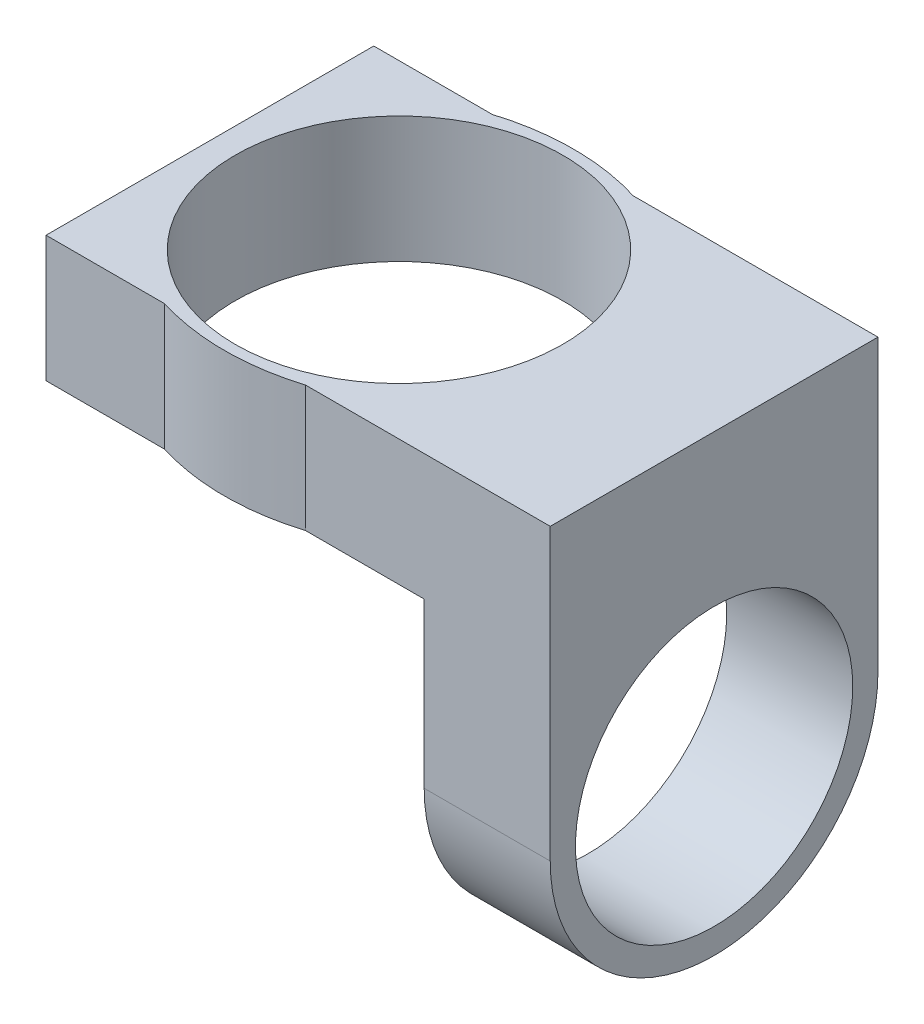
SolidWorks part; units mm, degrees
ref_plane "Front Plane" through (0, 0, 0) normal (0, 0, 1) x (1, 0, 0)
ref_plane "Top Plane" through (0, 0, 0) normal (0, 1, 0) x (1, 0, 0)
ref_plane "Right Plane" through (0, 0, 0) normal (1, 0, 0) x (0, 0, -1)
sketch "Sketch1" plane through (0, 0, 0) normal (1, 0, 0) x (0, 0, -1)
  circle A0 centre (0, 0) radius 11
  circle A1 centre (0, 0) radius 13
  dimension "D1" = 22
  dimension "D2" = 2
extrude "Boss-Extrude1" add sketch "Sketch1" along normal blind 10
ref_plane "Plane1" through (0, 13, 0) normal (0, 1, 0) x (1, 0, 0)
sketch "Sketch2" plane through (0, 13, 0) normal (0, 1, 0) x (1, 0, 0)
  line L0 (10, -13) -> (10, 13) construction
  line L1 (10, -13) -> (10, 13)
  line L2 (0, 13) -> (0, -13) construction
  line L3 (0, 13) -> (0, -13)
  line L4 (10, -13) -> (-30, -13)
  line L5 (-30, -13) -> (-30, 13)
  line L6 (-30, 13) -> (10, 13)
  line L7 (-15, 0) -> (-42.2528, 0) construction
  circle A0 centre (-15, 0) radius 11
  circle A1 centre (-15, 0) radius 13
  arc A2 (-9.412, -13) -> (-20.588, -13) centre (-15, 5.0473) cw
  arc A3 (-9.412, 13) -> (-20.588, 13) centre (-15, -5.0473) ccw
  point P12 (-15, -13.8453)
  dimension "D2" = 22
  dimension "D3" = 2
  dimension "D4" = 2
  dimension "D1" = 40
extrude "Boss-Extrude2" add sketch "Sketch2" against normal up to surface (13 mm away) contours L6 L3 L4 L1 region at (5, 13, 0) up to face at (10, 0, -13)
extrude "Boss-Extrude3" add sketch "Sketch2<3>" along normal blind 10 contours L6 L5 L4 L3 | L6 L3 L4 L1 | A1 L5 L4 | A1 L6 L5 | L6 A3 | A2 L4 region at (5, 13, 0) region at (-4.706, 13, 12.6998) region at (-15, 13, 13.3388) region at (-15, 13, -13.3388) region at (-17.794, 13, 12.6998)
sketch "Sketch2<3>" plane through (0, 13, 0) normal (0, 1, 0) x (1, 0, 0) same geometry as "Sketch2"
ref_point "Point1"
